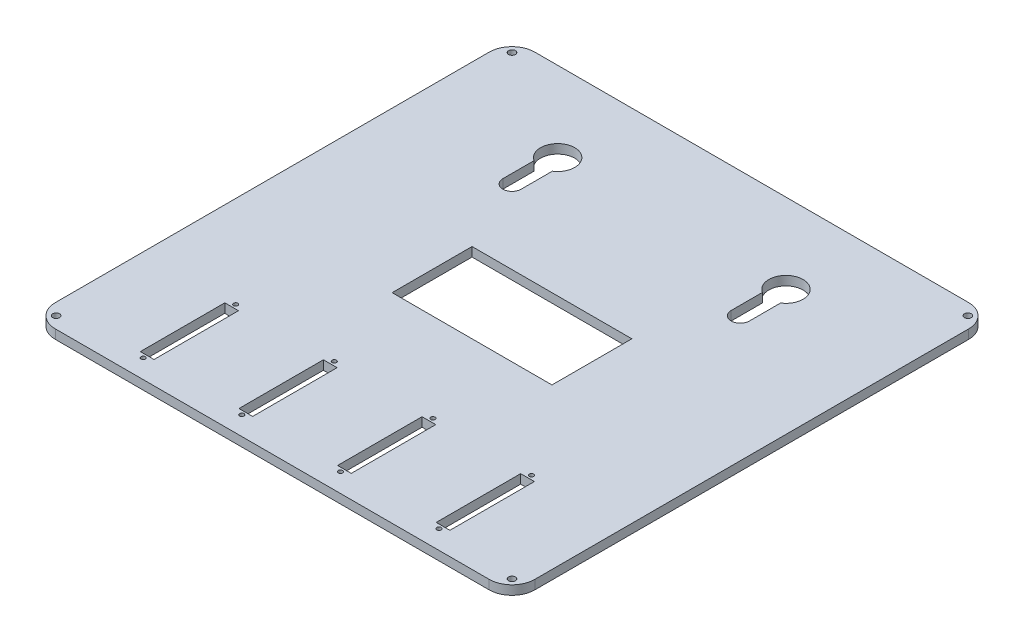
SolidWorks part; units mm, degrees
ref_plane "Front Plane" through (0, 0, 0) normal (0, 0, 1) x (1, 0, 0)
ref_plane "Top Plane" through (0, 0, 0) normal (0, 1, 0) x (1, 0, 0)
ref_plane "Right Plane" through (0, 0, 0) normal (1, 0, 0) x (0, 0, -1)
sketch "Sketch1" plane through (0, 0, 0) normal (0, 1, 0) x (1, 0, 0)
  line L0 (-101, -101) -> (-101, 101)
  line L5 (-105, -105) -> (105, -105)
  line L6 (-105, -105) -> (-105, 105)
  line L7 (-105, 105) -> (105, 105)
  line L8 (105, -105) -> (105, 105)
  line L9 (-101, 101) -> (101, 101)
  line L10 (101, -101) -> (101, 101)
  line L11 (-101, -101) -> (101, -101)
  line L12 (-101, 101) -> (-99.8333, 99.8333) construction
  line L13 (-55, 0) -> (55, 0) construction
  line L14 (-101, -101) -> (-99.8333, -99.8333) construction
  line L15 (0, -55) -> (0, 55) construction
  line L16 (101, -101) -> (99.8333, -99.8333) construction
  line L17 (101, 101) -> (99.8333, 99.8333) construction
  circle A1 centre (-99.8333, 99.8333) radius 1.5
  circle A2 centre (-99.8333, -99.8333) radius 1.5
  circle A3 centre (99.8333, -99.8333) radius 1.5
  circle A4 centre (99.8333, 99.8333) radius 1.5
  point P0 (0, 0)
  point P6 (-105, 0)
  point P7 (0, 105)
  dimension "D3" = 4
  dimension "D4" = 3
  dimension "D1" = 210
  dimension "D2" = 210
  dimension "D5" = 1.65
  dimension "D6" = 45
extrude "MainExtrude" add sketch "Sketch1" along normal mid plane 4 contours L6 L5 L8 L7
extrude "ScrewHoles" cut sketch "Sketch1<6>" along normal mid plane 4 contours A1 | A2 | A3 | A4
sketch "Sketch1<6>" plane through (0, 0, 0) normal (0, 1, 0) x (1, 0, 0) same geometry as "Sketch1"
fillet "RoundedCorners" radius 10 4 edges at (-105, 0, -105) (-105, 0, 105) (105, 0, -105) (105, 0, 105)
sketch "Sketch2" plane through (0, 2, 0) normal (0, 1, 0) x (1, 0, 0)
  line L0 (-50, 70) -> (-50, 50) construction
  line L1 (-67.8, -58) -> (-61.8, -58)
  line L2 (-67.8, -58) -> (-67.8, -95)
  line L3 (-67.8, -95) -> (-61.8, -95)
  line L4 (-61.8, -58) -> (-61.8, -95)
  line L5 (-24.6, -58) -> (-18.6, -58)
  line L6 (-24.6, -58) -> (-24.6, -95)
  line L7 (-24.6, -95) -> (-18.6, -95)
  line L8 (-18.6, -58) -> (-18.6, -95)
  line L9 (18.6, -58) -> (24.6, -58)
  line L10 (18.6, -58) -> (18.6, -95)
  line L11 (18.6, -95) -> (24.6, -95)
  line L12 (24.6, -58) -> (24.6, -95)
  line L13 (61.8, -58) -> (67.8, -58)
  line L14 (61.8, -58) -> (61.8, -95)
  line L15 (61.8, -95) -> (67.8, -95)
  line L16 (67.8, -58) -> (67.8, -95)
  line L17 (-95, -105) -> (95, -105) construction
  line L19 (-67.8, -58) -> (-105, -58) construction
  line L20 (-105, -95) -> (-105, 95) construction
  line L21 (-61.8, -58) -> (-24.6, -58) construction
  line L22 (-18.6, -58) -> (18.6, -58) construction
  line L23 (24.6, -58) -> (61.8, -58) construction
  line L25 (-105, 60) -> (-50, 60) construction
  line L26 (-95, 105) -> (95, 105) construction
  line L30 (-54, 50) -> (-54, 63.6557)
  line L31 (-46, 50) -> (-46, 63.6557)
  line L32 (0, -2.2) -> (0, 2.2) construction
  line L33 (46, 50) -> (46, 63.6557)
  line L34 (54, 50) -> (54, 63.6557)
  line L36 (35, -17.5) -> (-35, -17.5)
  line L37 (35, -17.5) -> (35, 17.5)
  line L38 (35, 17.5) -> (-35, 17.5)
  line L39 (-35, -17.5) -> (-35, 17.5)
  arc A0 (-54, 50) -> (-46, 50) centre (-50, 50) ccw
  arc A4 (-46, 63.6557) -> (-54, 63.6557) centre (-50, 70) ccw
  arc A5 (54, 50) -> (46, 50) centre (50, 50) cw
  arc A6 (46, 63.6557) -> (54, 63.6557) centre (50, 70) cw
  circle A7 centre (-64.8, -96.75) radius 0.95
  circle A8 centre (-64.8, -56.25) radius 0.95
  circle A9 centre (-21.6, -56.25) radius 0.95
  circle A10 centre (-21.6, -96.75) radius 0.95
  circle A11 centre (21.6, -56.25) radius 0.95
  circle A12 centre (21.6, -96.75) radius 0.95
  circle A13 centre (64.8, -56.25) radius 0.95
  circle A14 centre (64.8, -96.75) radius 0.95
  point P30 (0, 17.5)
  point P40 (-50, 60)
  point P42 (0, 0)
  point P48 (-35, 0)
  point P53 (0, 0)
  point P54 (-64.8, -95)
  point P58 (-61.8, -76.5)
  point P59 (-64.8, -58)
  point P60 (-21.6, -58)
  point P61 (0, 0)
  point P71 (-21.6, -95)
  dimension "D7" = 15
  dimension "D8" = 4
  dimension "D16" = 1.9
  dimension "D17" = 43.2
  dimension "D18" = 4
  dimension "D1" = 6
  dimension "D2" = 37
  dimension "D3" = 37.2
  dimension "D4" = 10
  dimension "D5" = 55
  dimension "D6" = 45
  dimension "D9" = 20
  dimension "D10" = 70
  dimension "D11" = 35
  dimension "D12" = 50
  dimension "D13" = 50
  dimension "D14" = 40.5
  dimension "D15" = 20.25
extrude "Knotches/Sliders" cut sketch "Sketch2" against normal up to surface (4 mm away) up to face at (-99.8333, -2, 98.3333)
